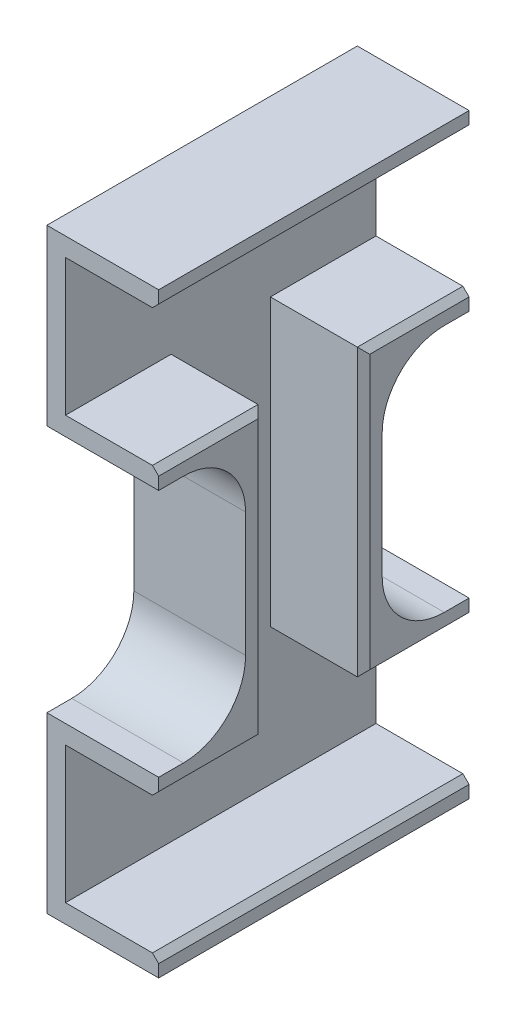
SolidWorks part; units mm, degrees
material "Custom Plastic"
ref_plane "Front Plane" through (0, 0, 0) normal (0, 0, 1) x (1, 0, 0)
ref_plane "Top Plane" through (0, 0, 0) normal (0, 1, 0) x (1, 0, 0)
ref_plane "Right Plane" through (0, 0, 0) normal (1, 0, 0) x (0, 0, -1)
sketch "Sketch1" plane through (0, 0, 0) normal (1, 0, 0) x (0, 0, -1)
  line L1 (0, 0) -> (50, 0)
  line L2 (0, 0) -> (0, 28)
  line L3 (0, 28) -> (50, 28)
  line L4 (50, 0) -> (50, 28)
  line L5 (14, 28) -> (36, 28)
  line L6 (14, 28) -> (14, 68)
  line L7 (14, 68) -> (36, 68)
  line L8 (36, 28) -> (36, 68)
  line L9 (0, 68) -> (50, 68)
  line L10 (0, 68) -> (0, 96)
  line L11 (0, 96) -> (50, 96)
  line L12 (50, 68) -> (50, 96)
  point P13 (25, 68)
  point P14 (25, 96)
  dimension "D1" = 28
  dimension "D2" = 40
  dimension "D3" = 50
  dimension "22" = 22
extrude "Boss-Extrude1" add sketch "Sketch1" along normal blind 18 contours L9 L12 L11 L10 L7 | L3 L8 L7 L6 | L1 L4 L3 L2 region at (0, 14, -25) region at (0, 48, -25) region at (0, 82, -25)
sketch "Sketch2" plane through (18, 0, 0) normal (1, 0, 0) x (0, 0, -1)
  line L0 (0, 0) -> (0, 28) construction
  line L1 (0, 93) -> (50, 93)
  line L2 (0, 93) -> (0, 71)
  line L3 (0, 71) -> (50, 71)
  line L4 (50, 93) -> (50, 71)
  line L5 (17, 71) -> (33, 71)
  line L6 (17, 71) -> (17, 25)
  line L7 (17, 25) -> (33, 25)
  line L8 (33, 71) -> (33, 25)
  line L9 (0, 25) -> (50, 25)
  line L10 (0, 25) -> (0, 3)
  line L11 (0, 3) -> (50, 3)
  line L12 (50, 25) -> (50, 3)
  line L13 (50, 68) -> (50, 96) construction
  line L14 (50, 0) -> (50, 28) construction
  line L15 (0, 0) -> (50, 0) construction
  line L16 (0, 68) -> (0, 96) construction
  point P14 (0, 14)
  point P15 (0, 14)
  point P22 (25, 0)
  point P23 (25, 25)
  point P24 (0, 82)
  line M16 (0, 28) -> (0, 0)
  line M18 (50, 0) -> (50, 28)
  line M22 (50, 68) -> (50, 96)
  line M24 (0, 96) -> (0, 68)
  dimension "D1" = 22
  dimension "D2" = 16
extrude "Cut-Extrude1" cut sketch "Sketch2" against normal blind 15 contours L3 L1 M24 M22 | L8 L3 L6 L7 | L11 L9 L7 M16 M18 region at (18, 82, -25) region at (18, 48, -25) region at (18, 14, -25)
fillet "Fillet1" radius 10 4 edges at (9, 28, -36) (9, 68, -36) (9, 28, -14) (9, 68, -14)
chamfer "Chamfer1" distance 1 angle 45 8 edges at (18, 3, -25) (18, 93, -25) (18, 25, -8.5) (18, 48, -17) (18, 71, -8.5) (18, 25, -41.5) (18, 48, -33) (18, 71, -41.5)
